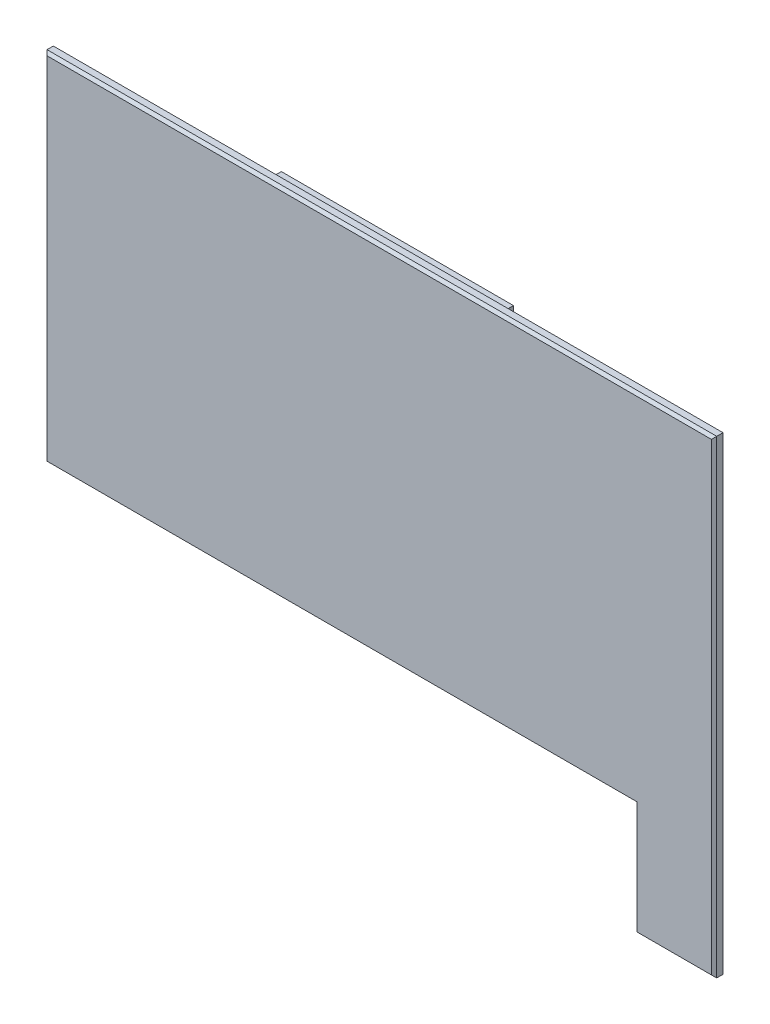
SolidWorks part; units mm, degrees
ref_plane "Front Plane" through (0, 0, 0) normal (0, 0, 1) x (1, 0, 0)
ref_plane "Top Plane" through (0, 0, 0) normal (0, 1, 0) x (1, 0, 0)
ref_plane "Right Plane" through (0, 0, 0) normal (1, 0, 0) x (0, 0, -1)
sketch "Sketch1" plane through (0, 0, 0) normal (0, 0, 1) x (1, 0, 0)
  line L1 (22.6281, 79.7492) -> (-78.3719, 79.7492)
  line L2 (22.6281, 79.7492) -> (22.6281, 26.2389)
  line L3 (10.6281, 26) -> (-78.3719, 26)
  line L4 (-78.3719, 79.7492) -> (-78.3719, 26)
  line L7 (22.6281, 26.2389) -> (22.6281, 9)
  line L8 (22.6281, 9) -> (10.6281, 9)
  line L9 (10.6281, 26) -> (10.6281, 9)
  line L10 (24.6281, 80.7492) -> (24.6281, -1) construction
  line L11 (-79.3719, 81.7492) -> (23.6281, 81.7492) construction
  line L13 (-80.3719, 23.5916) -> (-80.3719, 80.7492) construction
  line L14 (23.6281, -2) -> (-186.5288, -2) construction
  dimension "D1" = 2
  dimension "D2" = 2
  dimension "D3" = 2
  dimension "D4" = 11
  dimension "D5" = 12
  dimension "D6" = 17
extrude "main" add sketch "Sketch1" along normal blind 1.75
chamfer "Chamfer1" distance 0.4 angle 45 12 edges at (16.6281, 9, 1.75) (10.6281, 17.5, 1.75) (-33.8719, 26, 1.75) (-78.3719, 52.8746, 1.75) (-27.8719, 79.7492, 1.75) (22.6281, 44.3746, 1.75) (-78.3719, 52.8746, 0) (-33.8719, 26, 0) (10.6281, 17.5, 0) (16.6281, 9, 0) (22.6281, 44.3746, 0) (-27.8719, 79.7492, 0)
sketch "Sketch2" plane through (0, 0, 0) normal (0, 0, -1) x (-1, 0, 0)
  line L21 (12.3719, 76.6492) -> (47.3719, 76.6492)
  line L22 (12.3719, 76.6492) -> (12.3719, 74.6492)
  line L40 (12.3719, 74.6492) -> (47.3719, 74.6492)
  line L48 (47.3719, 76.6492) -> (47.3719, 74.6492)
  line L65 (12.3719, 30.8492) -> (47.3719, 30.8492)
  line L66 (12.3719, 30.8492) -> (12.3719, 28.8492)
  line L67 (65.2719, 76.6492) -> (55.2719, 76.6492)
  line L68 (-9.6281, 76.7492) -> (65.3719, 76.7492) construction
  line L69 (65.2719, 76.6492) -> (65.2719, 66.6492)
  line L70 (65.3719, 76.7492) -> (65.3719, 28.7492) construction
  line L71 (55.2719, 76.6492) -> (55.2719, 74.6492)
  line L72 (55.2719, 74.6492) -> (63.2719, 74.6492)
  line L73 (63.2719, 74.6492) -> (63.2719, 66.6492)
  line L74 (63.2719, 66.6492) -> (65.2719, 66.6492)
  line L75 (0.4719, 76.6492) -> (-9.5281, 76.6492)
  line L76 (-9.5281, 76.6492) -> (-9.5281, 66.6492)
  line L77 (-9.6281, 28.7492) -> (-9.6281, 76.7492) construction
  line L78 (-9.5281, 66.6492) -> (-7.5281, 66.6492)
  line L79 (-7.5281, 66.6492) -> (-7.5281, 74.6492)
  line L80 (-7.5281, 74.6492) -> (0.4719, 74.6492)
  line L81 (0.4719, 74.6492) -> (0.4719, 76.6492)
  line L82 (65.2719, 38.8492) -> (65.2719, 28.8492)
  line L83 (65.2719, 28.8492) -> (55.2719, 28.8492)
  line L84 (65.3719, 28.7492) -> (-9.6281, 28.7492) construction
  line L85 (55.2719, 28.8492) -> (55.2719, 30.8492)
  line L86 (55.2719, 30.8492) -> (63.2719, 30.8492)
  line L87 (63.2719, 30.8492) -> (63.2719, 38.8492)
  line L88 (63.2719, 38.8492) -> (65.2719, 38.8492)
  line L89 (0.4719, 28.8492) -> (-9.5281, 28.8492)
  line L90 (-9.5281, 28.8492) -> (-9.5281, 38.8492)
  line L91 (0.4719, 28.8492) -> (0.4719, 30.8492)
  line L92 (0.4719, 30.8492) -> (-7.5281, 30.8492)
  line L93 (-7.5281, 30.8492) -> (-7.5281, 38.8492)
  line L94 (-7.5281, 38.8492) -> (-9.5281, 38.8492)
  line L95 (12.3719, 28.8492) -> (47.3719, 28.8492)
  line L96 (47.3719, 30.8492) -> (47.3719, 28.8492)
  line L97 (-22.6281, 9) -> (-22.6281, 79.7492) construction
  dimension "D1" = 0.1
  dimension "D2" = 0.1
  dimension "D3" = 2
  dimension "D4" = 10
  dimension "D5" = 0.1
  dimension "D6" = 0.1
  dimension "D7" = 35
  dimension "D8" = 35
extrude "interlock1" add sketch "Sketch2" along normal offset from surface (2.2 mm away) 0.2 offset beyond the face yes
sketch "Sketch3" plane through (0, -1.0223, -47.6285) normal (0, 0.342, -0.9397) x (-1, 0, 0)
  circle A0 centre (-15.6896, 82.1319) radius 3.25
  circle A1 centre (72.0151, 82.1319) radius 3.25
  circle A2 centre (-15.6896, 32.9872) radius 3.25
  dimension "D1" = 6.5
extrude "interlock2" add sketch "Sketch3" along normal blind 3 from surface starting at face at (-14.9052, 38.3831, 0)
sketch "Sketch5" plane through (0, 0, -2.2) normal (0, 0, -1) x (-1, 0, 0)
  line L0 (47.3719, 74.6492) -> (12.3719, 74.6492) construction
  line L1 (47.3719, 74.6492) -> (12.3719, 74.6492)
  line L2 (47.3719, 74.6492) -> (47.3719, 77.1492)
  line L3 (47.3719, 77.1492) -> (12.3719, 77.1492)
  line L4 (12.3719, 74.6492) -> (12.3719, 77.1492)
  line L5 (12.3719, 74.6492) -> (12.3719, 76.6492) construction
  line L6 (-9.6281, 76.7492) -> (65.3719, 76.7492) construction
  line L8 (47.3719, 30.8492) -> (12.3719, 30.8492)
  line L9 (47.3719, 30.8492) -> (47.3719, 28.3492)
  line L10 (47.3719, 28.3492) -> (12.3719, 28.3492)
  line L11 (12.3719, 30.8492) -> (12.3719, 28.3492)
  dimension "D1" = 0.4
extrude "latch" add sketch "Sketch5" along normal blind 0.8
